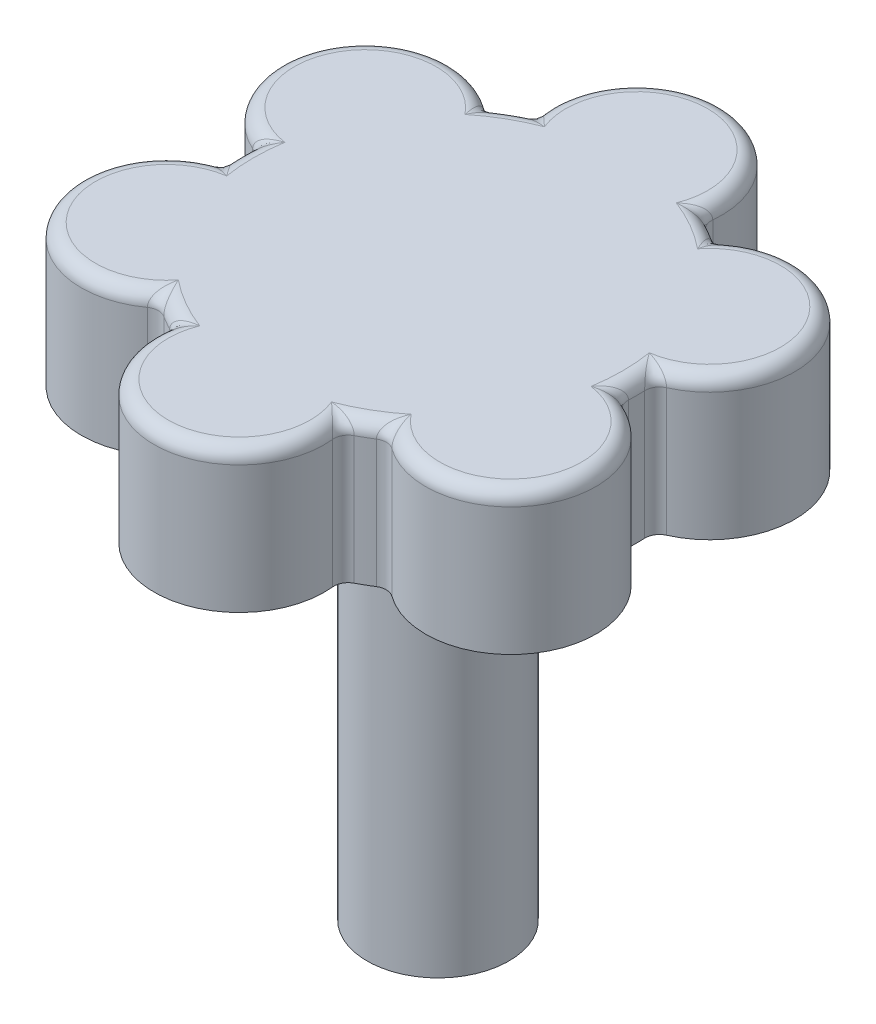
SolidWorks part; units mm, degrees
ref_plane "前视基准面" through (0, 0, 0) normal (0, 0, 1) x (1, 0, 0)
ref_plane "上视基准面" through (0, 0, 0) normal (0, 1, 0) x (1, 0, 0)
ref_plane "右视基准面" through (0, 0, 0) normal (1, 0, 0) x (0, 0, -1)
sketch "Sketch1" plane through (0, 0, 0) normal (0, 1, 0) x (1, 0, 0)
  line L0 (0, 0) -> (0, 12.0651) construction
  circle A0 centre (0, 0) radius 10 construction
  arc A1 (-6.9706, 0.6408) -> (-6.9706, -0.6408) centre (0, 0) ccw
  arc A2 (0, 10) -> (-2.9303, 6.3571) centre (0, 7) ccw
  arc A3 (0, 10) -> (2.9303, 6.3571) centre (0, 7) cw
  arc A4 (8.6603, 5) -> (6.9706, 0.6408) centre (6.0622, 3.5) cw
  arc A5 (8.6603, 5) -> (4.0403, 5.7163) centre (6.0622, 3.5) ccw
  arc A6 (8.6603, -5) -> (4.0403, -5.7163) centre (6.0622, -3.5) cw
  arc A7 (8.6603, -5) -> (6.9706, -0.6408) centre (6.0622, -3.5) ccw
  arc A8 (0, -10) -> (-2.9303, -6.3571) centre (0, -7) cw
  arc A9 (0, -10) -> (2.9303, -6.3571) centre (0, -7) ccw
  arc A10 (-8.6603, -5) -> (-6.9706, -0.6408) centre (-6.0622, -3.5) cw
  arc A11 (-8.6603, -5) -> (-4.0403, -5.7163) centre (-6.0622, -3.5) ccw
  arc A12 (-8.6603, 5) -> (-4.0403, 5.7163) centre (-6.0622, 3.5) cw
  arc A13 (-8.6603, 5) -> (-6.9706, 0.6408) centre (-6.0622, 3.5) ccw
  arc A14 (-2.9303, 6.3571) -> (-4.0403, 5.7163) centre (0, 0) ccw
  arc A15 (4.0403, 5.7163) -> (2.9303, 6.3571) centre (0, 0) ccw
  arc A16 (6.9706, -0.6408) -> (6.9706, 0.6408) centre (0, 0) ccw
  arc A17 (2.9303, -6.3571) -> (4.0403, -5.7163) centre (0, 0) ccw
  arc A18 (-4.0403, -5.7163) -> (-2.9303, -6.3571) centre (0, 0) ccw
  dimension "D1" = 6
extrude "Boss-Extrude1" add sketch "Sketch1" along normal blind 5
fillet "Fillet1" radius 0.5 12 edges at (3.5, 5, -6.0622) (8.6603, 5, -5) (7, 5, 0) (8.6603, 5, 5) (3.5, 5, 6.0622) (0, 5, 10) (-3.5, 5, 6.0622) (-8.6603, 5, 5) (-7, 5, 0) (-8.6603, 5, -5) (-3.5, 5, -6.0622) (0, 5, -10)
fillet "Fillet2" radius 0.5 24 edges at (2.8461, 4.7597, -6.3156) (4.0464, 4.7597, -5.6226) (6.8925, 4.7597, -0.693) (6.8925, 4.7597, 0.693) (4.0464, 4.7597, 5.6226) (2.8461, 4.7597, 6.3156) (-2.8461, 4.7597, 6.3156) (-4.0464, 4.7597, 5.6226) (-6.8925, 4.7597, 0.693) (-6.8925, 4.7597, -0.693) (-2.8461, 4.7597, -6.3156) (-4.0464, 4.7597, -5.6226) (2.9303, 2.25, -6.3571) (4.0403, 2.25, -5.7163) (6.9706, 2.25, -0.6408) (6.9706, 2.25, 0.6408) (4.0403, 2.25, 5.7163) (2.9303, 2.25, 6.3571) (-2.9303, 2.25, 6.3571) (-4.0403, 2.25, 5.7163) (-6.9706, 2.25, 0.6408) (-6.9706, 2.25, -0.6408) (-2.9303, 2.25, -6.3571) (-4.0403, 2.25, -5.7163)
sketch "Sketch2" plane through (0, 0, 0) normal (0, -1, 0) x (1, 0, 0)
  circle A0 centre (0, 0) radius 2.5
extrude "Boss-Extrude2" add sketch "Sketch2" along normal blind 15
